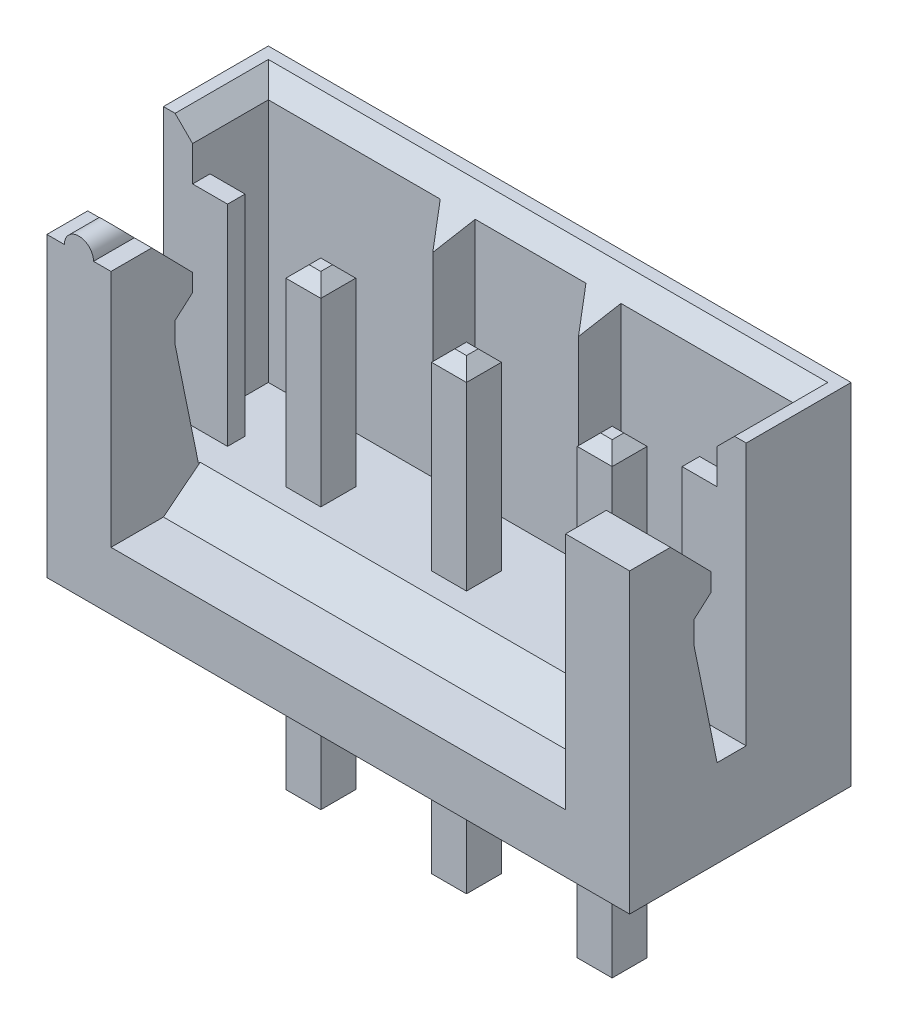
SolidWorks part; units mm, degrees
ref_plane "Спереди" through (0, 0, 0) normal (0, 0, 1) x (1, 0, 0)
ref_plane "Сверху" through (0, 0, 0) normal (0, 1, 0) x (1, 0, 0)
ref_plane "Справа" through (0, 0, 0) normal (1, 0, 0) x (0, 0, -1)
sketch "Эскиз1" plane through (0, 0, 0) normal (0, 1, 0) x (1, 0, 0)
  line L1 (0, 0) -> (10, 0)
  line L2 (0, 0) -> (0, -3.8)
  line L3 (0, -3.8) -> (10, -3.8)
  line L4 (10, 0) -> (10, -3.8)
  dimension "D1" = 10
  dimension "D2" = 3.8
extrude "Бобышка-Вытянуть1" add sketch "Эскиз1" along normal blind 6
sketch "Эскиз2" plane through (0, 6, 0) normal (0, 1, 0) x (1, 0, 0)
  line L0 (0, 0) -> (0, -3.8) construction
  line L1 (0.5, -0.5) -> (9.5, -0.5)
  line L2 (0.5, -0.5) -> (0.5, -1.5)
  line L3 (1.1, -3.3) -> (8.9, -3.3)
  line L5 (5, 0) -> (5, -3.8) construction
  line L6 (10, 0) -> (0, 0) construction
  line L7 (0, -3.8) -> (10, -3.8) construction
  line L9 (0.5, -1.5) -> (1.1, -1.5)
  line L10 (1.1, -1.5) -> (1.1, -3.3)
  line L11 (8.9, -1.5) -> (8.9, -3.3)
  line L12 (9.5, -1.5) -> (8.9, -1.5)
  line L13 (9.5, -0.5) -> (9.5, -1.5)
  line L14 (0.5, -1.5) -> (0.5, -1.8) construction
  line L15 (0.5, -1.8) -> (1.1, -1.8) construction
  point P13 (5, -3.3)
  point P14 (5, -0.5)
  point P16 (5, -3.3)
  point P20 (5, -0.5)
  dimension "D1" = 0.5
  dimension "D2" = 0.5
  dimension "D3" = 2.8
  dimension "D4" = 0.3
  dimension "D5" = 0.6
  dimension "D6" = 1.3
extrude "Вырез-Вытянуть1" cut sketch "Эскиз2" against normal blind 5
sketch "Эскиз3" plane through (0, 0, 0) normal (-1, 0, 0) x (0, 0, 1)
  line L0 (1.8, 6) -> (1.8, 1.5)
  line L1 (0, 6) -> (3.8, 6) construction
  line L2 (1.8, 1.5) -> (2.3, 1.5)
  line L3 (2.3, 1.5) -> (2.7, 3.4596)
  line L4 (0, 6) -> (0, 0) construction
  line L5 (3.8, 5.1) -> (3.1, 5.1)
  line L6 (3.8, 6) -> (3.8, 0) construction
  line L8 (3.1, 5.1) -> (2.4, 4.3859)
  line L9 (2.4, 4.3859) -> (2.4, 4.0859)
  line L10 (2.4, 4.0859) -> (2.7, 3.8213)
  line L11 (2.7, 3.8213) -> (2.7, 3.4596)
  line L12 (1.8, 6) -> (3.8, 6)
  line L13 (3.8, 6) -> (3.8, 5.1)
  dimension "D1" = 1.8
  dimension "D2" = 4.5
  dimension "D3" = 0.9
  dimension "D4" = 0.7
  dimension "D5" = 1.4
  dimension "D6" = 1.1
  dimension "D7" = 2
  dimension "D8" = 0.4
  dimension "D9" = 1
  dimension "D10" = 0.3
  dimension "D11" = 0.5
extrude "Вырез-Вытянуть2" cut sketch "Эскиз3" against normal through all
sketch "Эскиз4" plane through (0, 0, 3.8) normal (0, 0, 1) x (1, 0, 0)
  line L0 (0, 5.1) -> (1.1, 5.1) construction
  line L1 (10, 5.1) -> (0, 5.1) construction
  line L3 (0.3, 5.1) -> (0.8, 5.1)
  arc A0 (0.8, 5.1) -> (0.3, 5.1) centre (0.55, 5.1) ccw
  point P8 (0, 0)
  dimension "D1" = 0.5
  dimension "D2" = 1.1
extrude "Бобышка-Вытянуть2" add sketch "Эскиз4" against normal up to surface (0.7 mm away) up to face at (0.55, 4.7429, 2.75)
sketch "Эскиз5" plane through (0, 0, 3.8) normal (0, 0, 1) x (1, 0, 0)
  line L0 (10, 5.1) -> (0.8, 5.1) construction
  line L1 (1.1, 5.1) -> (8.9, 5.1)
  line L2 (1.1, 5.1) -> (1.1, 1)
  line L3 (1.1, 1) -> (8.9, 1)
  line L6 (0, 5.1) -> (0, 0) construction
  line L8 (5, 1) -> (5, 5.1) construction
  line L9 (8.9, 5.1) -> (8.9, 1)
  line L11 (0, 0) -> (10, 0) construction
  line L12 (5, 0) -> (5, 5.1) construction
  line L13 (1.1, 1) -> (8.9, 1) construction
  point P14 (5, 3.05)
  dimension "D1" = 1.1
extrude "Вырез-Вытянуть3" cut sketch "Эскиз5" against normal up to next
sketch "Эскиз6" plane through (0.5, 0, 0) normal (1, 0, 0) x (0, 0, -1)
  line L0 (-0.5, 1) -> (-1.5, 1) construction
  line L2 (-2.9, 1) -> (-2.27, 1.5)
  line L3 (-2.27, 1.5) -> (-0.5, 1.5)
  line L4 (-0.5, 1) -> (-0.5, 6) construction
  line L5 (-0.5, 1.5) -> (-0.5, 1)
  line L6 (-0.5, 1) -> (-2.9, 1)
  line L8 (-3.8, 5.1) -> (-3.8, 1) construction
  point P0 (-2.8028, 1)
  dimension "D1" = 0.5
  dimension "D2" = 1.77
  dimension "D3" = 0.9
extrude "Бобышка-Вытянуть3" add sketch "Эскиз6" along normal up to next
sketch "Эскиз9" plane through (0, 6, 0) normal (0, 1, 0) x (1, 0, 0)
  line L0 (3.45, -0.5) -> (3.75, -0.9284)
  line L1 (9.5, -0.5) -> (0.5, -0.5) construction
  line L2 (3.75, -0.5) -> (3.75, -0.9284) construction
  line L3 (9.5, -0.5) -> (0.5, -0.5) construction
  line L4 (4.05, -0.5) -> (3.75, -0.9284)
  line L5 (3.45, -0.5) -> (4.05, -0.5)
  dimension "D1" = 0.6
  dimension "D2" = 35
  dimension "D3" = 2.95
extrude "Бобышка-Вытянуть5" add sketch "Эскиз9" against normal up to next
sketch "Эскиз11" plane through (0, 0, 0) normal (0, -1, 0) x (1, 0, 0)
  line L1 (1.5, 3.2) -> (3.5, 3.2)
  line L2 (1.5, 3.2) -> (1.5, 0)
  line L3 (1.5, 0) -> (3.5, 0)
  line L4 (3.5, 3.2) -> (3.5, 0)
  line L5 (1.5, 3.2) -> (3.5, 0) construction
  line L6 (1.5, 0) -> (3.5, 3.2) construction
  line L7 (10, 0) -> (0, 0) construction
  line L9 (2.1, 2) -> (2.9, 2)
  line L10 (2.1, 2) -> (2.1, 1.2)
  line L11 (2.1, 1.2) -> (2.9, 1.2)
  line L12 (2.9, 2) -> (2.9, 1.2)
  line L13 (2.1, 2) -> (2.9, 1.2) construction
  line L14 (2.1, 1.2) -> (2.9, 2) construction
  point P0 (2.5, 1.6)
  point P8 (2.5, 1.6)
  dimension "D1" = 2.5
  dimension "D2" = 1.6
  dimension "D3" = 2
  dimension "D4" = 0.8
extrude "Вырез-Вытянуть5" cut sketch "Эскиз11" against normal blind 0.3
sketch "Эскиз15" plane through (0, 0, 0) normal (0, -1, 0) x (1, 0, 0)
  line L0 (2.1, 2) -> (2.9, 1.2) construction
  circle A0 centre (2.5, 1.6) radius 0.05
  point P4 (2.5, 1.6)
  dimension "D1" = 0.1
extrude "Вырез-Вытянуть6" cut sketch "Эскиз15" against normal blind 0.1
ref_point "Точка1"
chamfer "Фаска7" distance 0.3 angle 45 7 edges at (1.5, 0.3, 1.6) (2.5, 0.3, 3.2) (3.5, 0.3, 1.6) (2.9, 0.3, 1.6) (2.5, 0.3, 2) (2.1, 0.3, 1.6) (2.5, 0.3, 1.2)
pattern_linear "Линейный массив2" count 2 spacing 2.5 along (1, 0, 0) of "Бобышка-Вытянуть5"
sketch "Эскиз7" plane through (0, 0, 0) normal (0, -1, 0) x (1, 0, 0)
  line L0 (10, 0) -> (3.5, 0) construction
  line L1 (2.2, 1.9) -> (2.8, 1.9)
  line L2 (2.2, 1.9) -> (2.2, 1.3)
  line L3 (2.2, 1.3) -> (2.8, 1.3)
  line L4 (2.8, 1.9) -> (2.8, 1.3)
  line L5 (2.2, 1.9) -> (2.8, 1.3) construction
  line L6 (2.2, 1.3) -> (2.8, 1.9) construction
  line L7 (0, 0) -> (0, 3.8) construction
  point P0 (2.5, 1.6)
  dimension "D1" = 0.6
  dimension "D2" = 1.6
  dimension "D3" = 2.5
extrude "Бобышка-Вытянуть4" add sketch "Эскиз7" against normal blind 4.8 and the other way blind 3.2
chamfer "Фаска6" distance 0.2 angle 45 8 edges at (2.5, -3.2, 1.3) (2.2, -3.2, 1.6) (2.5, -3.2, 1.9) (2.8, -3.2, 1.6) (2.5, 4.8, 1.9) (2.2, 4.8, 1.6) (2.5, 4.8, 1.3) (2.8, 4.8, 1.6)
pattern_linear "Линейный массив1" count 3 spacing 2.5 along (1, 0, 0) of "Бобышка-Вытянуть4", "Фаска6", "Фаска7", "Вырез-Вытянуть5"
sketch "Эскиз10" plane through (0.5, 0, 0) normal (1, 0, 0) x (0, 0, -1)
  line L0 (-1, 6) -> (-0.2, 6)
  line L1 (-0.2, 6) -> (-1, 5.2)
  line L3 (-1, 5.2) -> (-1, 5.1)
  line L4 (-0.5, 6) -> (-1.5, 6) construction
  line L5 (-1, 5.1) -> (-1.8, 5.1)
  line L6 (-1.8, 5.1) -> (-1.8, 6)
  line L7 (-1.8, 6) -> (-1, 6)
  line L8 (-1, 6) -> (-1, 5.1) construction
  dimension "D1" = 45
  dimension "D2" = 0.9
  dimension "D3" = 0.8
  dimension "D4" = 0.8
extrude "Вырез-Вытянуть4" cut sketch "Эскиз10" along normal up to surface (9 mm away) contours L1 L3 L5 L6 L7 L0 up to face at (9.5, 3.75, 1)
chamfer "Фаска5" distance 0.3 angle 45 2 edges at (9.5, 6, 1) (0.5, 6, 1)
equation "\"PINS\" = 3"
equation "\"D1@Линейный массив2\"= \"GUIDE_MASS\""
equation "\"PIN_MASS\"= \"PINS\""
equation "\"D1@Линейный массив1\"=\"PIN_MASS\""
equation "\"GUIDE_MASS\" = \"PINS\" - 1"
equation "\"D1@Эскиз1\"= 5 + ( 2.5 * ( \"PIN_MASS\" - 1 ) )"
